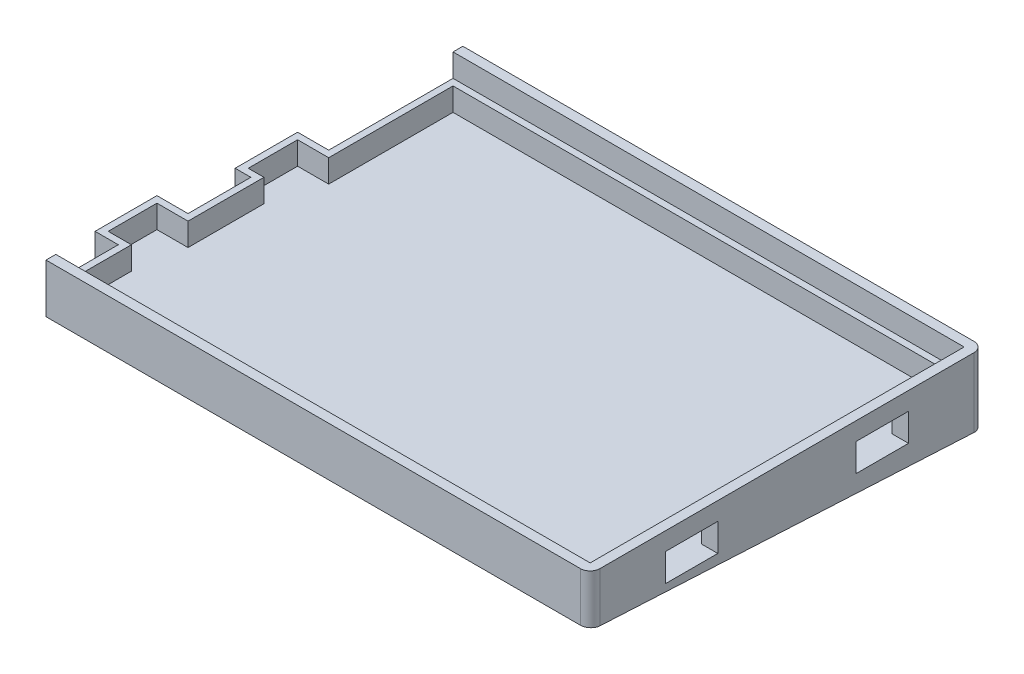
SolidWorks part; units mm, degrees
note: The reader was unsure of these and kept them because the rebuilt part matched: shared geometry of "Sketch3<3>", "Sketch5<4>", "Sketch5<6>".
ref_plane "Front Plane" through (0, 0, 0) normal (0, 0, 1) x (1, 0, 0)
ref_plane "Top Plane" through (0, 0, 0) normal (0, 1, 0) x (1, 0, 0)
ref_plane "Right Plane" through (0, 0, 0) normal (1, 0, 0) x (0, 0, -1)
sketch "Sketch3" plane through (0, 0, 0) normal (0, 1, 0) x (1, 0, 0)
  line L0 (0, 0) -> (0, 114.28)
  line L1 (0, 114.28) -> (-156.193, 114.28)
  line L2 (0, 0) -> (-163.3, 0)
  line L3 (-163.3, 0) -> (-163.3, 19.1)
  line L4 (-163.3, 19.1) -> (-170.4, 19.1)
  line L5 (-170.4, 19.1) -> (-170.4, 38)
  line L6 (-170.4, 38) -> (-160.9, 38)
  line L7 (-160.9, 38) -> (-160.9, 57.2)
  line L8 (-156.193, 114.28) -> (-156.193, 76.28)
  line L9 (-156.193, 76.28) -> (-165.693, 76.28)
  line L10 (-165.693, 76.28) -> (-165.693, 57.2)
  line L11 (-165.693, 57.2) -> (-160.9, 57.2)
  line L12 (3, -3) -> (-163.3, -3)
  line L13 (3, -3) -> (3, 117.28)
  line L14 (3, 117.28) -> (-156.193, 117.28)
  line L15 (-163.3, 0) -> (-163.3, -3)
  line L16 (-156.193, 117.28) -> (-156.193, 114.28)
  line L17 (0, 94.28) -> (3, 94.28)
  line L18 (0, 78.28) -> (3, 78.28)
  dimension "D1" = 114.28
  dimension "D2" = 156.193
  dimension "D3" = 163.3
  dimension "D4" = 19.1
  dimension "D5" = 18.9
  dimension "D6" = 7.1
  dimension "D7" = 9.5
  dimension "D8" = 19.2
  dimension "D9" = 38
  dimension "D10" = 9.5
  dimension "D11" = 3
  dimension "D12" = 16
  dimension "D13" = 20
extrude "Boss-Extrude2" add sketch "Sketch3" along normal blind 14 contours L14 L16 L1 L0 L2 L15 L12 L13 | L0 L17 L13 L14 L16 L1
extrude "Boss-Extrude3" add sketch "Sketch3<3>" against normal blind 1 contours L10 L11 L7 L6 L5 L4 L3 L2 L0 L1 L8 L9 | L14 L16 L1 L0 L2 L15 L12 L13
sketch "Sketch3<3>" plane through (0, 0, 0) normal (0, 1, 0) x (1, 0, 0) same geometry as "Sketch3"
sketch "Sketch4" plane through (3, 0, 0) normal (1, 0, 0) x (0, 0, -1)
  line L1 (117.28, -7.3036) -> (-3, -1)
  line L2 (-3, -1) -> (78.28, -1) construction
  line L5 (117.28, 14) -> (117.28, 0) construction
  line L6 (117.28, 0) -> (-3, 0)
  line L7 (-3, 14) -> (-3, -1) construction
  line L8 (-3, 0) -> (-3, -1)
  line L9 (117.28, 0) -> (117.28, -7.3036)
  dimension "D1" = 3
  dimension "D2" = 1
extrude "Boss-Extrude6" add sketch "Sketch4" against normal up to surface (159.193 mm away) up to face at (-156.193, -0.5, -95.28)
sketch "Sketch5" plane through (-156.193, 0, 0) normal (-1, 0, 0) x (0, 0, 1)
  line L0 (-76.28, 0) -> (3, 0)
  line L1 (0, 0) -> (3, 0) construction
  line L2 (3, 14) -> (3, -1) construction
  line L3 (3, 0) -> (3, -1)
  line L4 (3, -1) -> (-76.28, -5.1549)
  line L5 (-117.28, -7.3036) -> (3, -1) construction
  line L6 (-76.28, -5.1549) -> (-76.28, 0)
  line L7 (-19.1, 0) -> (-19.1, -2.1582)
  line L8 (-38, 0) -> (-38, -3.1487)
  line L9 (-57.2, 0) -> (-57.2, -4.1549)
  line M23 (3, -1) -> (-76.28, -1)
extrude "Boss-Extrude7" add sketch "Sketch5" along normal up to surface (4.707 mm away) contours L7 L4 M23
extrude "Boss-Extrude8" add sketch "Sketch5<4>" along normal up to surface (9.5 mm away) up to face at (-165.693, -0.5, -66.74)
sketch "Sketch5<4>" plane through (-156.193, 0, 0) normal (-1, 0, 0) x (0, 0, 1) same geometry as "Sketch5"
extrude "Boss-Extrude9" add sketch "Sketch5" along normal up to surface (7.107 mm away) contours L7 L4 M23 up to face at (-163.3, 4.3333, -5.3667)
extrude "Boss-Extrude10" add sketch "Sketch5<6>" along normal up to surface (14.207 mm away) up to face at (-170.4, -0.5, -28.55)
sketch "Sketch5<6>" plane through (-156.193, 0, 0) normal (-1, 0, 0) x (0, 0, 1) same geometry as "Sketch5"
sketch "Sketch7" plane through (0, 0, 0) normal (-1, 0, 0) x (0, 0, 1)
  line L0 (0, 0) -> (-20, 0)
  line L1 (3, 0) -> (-117.28, 0) construction
  line L2 (-20, 0) -> (-20, 14)
  line L3 (0, 14) -> (-78.28, 14) construction
  line L4 (-20, 14) -> (-36, 14)
  line L5 (-36, 14) -> (-36, 0)
  line L6 (-36, 0) -> (-20, 0)
  line L7 (-36, 8.5) -> (-20, 8.5)
  line M12 (-78.28, 0) -> (0, 0)
  dimension "D1" = 16
  dimension "D2" = 20
  dimension "D3" = 5.5
extrude "Cut-Extrude1" cut sketch "Sketch7" against normal blind 4 contours L7 L5 L2 M12
fillet "Fillet1" radius 3 1 edges at (3, 3.3482, -117.28)
fillet "Fillet2" radius 3 1 edges at (3, 6.5, 3)
sketch "Sketch8" plane through (0, 0, 0) normal (0, 1, 0) x (1, 0, 0)
  line L0 (-2, 112.28) -> (-154.193, 112.28)
  line L1 (-154.193, 112.28) -> (-154.193, 74.28)
  line L2 (-154.193, 74.28) -> (-163.693, 74.28)
  line L3 (-163.693, 74.28) -> (-163.693, 59.2)
  line L4 (-163.693, 59.2) -> (-158.9, 59.2)
  line L5 (-158.9, 59.2) -> (-158.9, 36)
  line L6 (-158.9, 36) -> (-168.4, 36)
  line L7 (-168.4, 36) -> (-168.4, 21.1)
  line L8 (-168.4, 21.1) -> (-161.3, 21.1)
  line L9 (-161.3, 21.1) -> (-161.3, 2)
  line L10 (-161.3, 2) -> (-2, 2)
  line L11 (-2, 2) -> (-2, 28)
  line L15 (-2, 28) -> (-2, 80.28)
  line L19 (-2, 92.28) -> (-2, 112.28)
  line L20 (3, 78.28) -> (3, 94.28)
  line L21 (3, 94.28) -> (0, 94.28)
  line L22 (0, 94.28) -> (0, 114.28)
  line L23 (0, 114.28) -> (-156.193, 114.28)
  line L24 (-156.193, 114.28) -> (-156.193, 76.28)
  line L25 (-156.193, 76.28) -> (-165.693, 76.28)
  line L26 (-165.693, 76.28) -> (-165.693, 57.2)
  line L27 (-165.693, 57.2) -> (-160.9, 57.2)
  line L28 (-160.9, 57.2) -> (-160.9, 38)
  line L29 (-160.9, 38) -> (-170.4, 38)
  line L30 (-170.4, 38) -> (-170.4, 19.1)
  line L31 (-170.4, 19.1) -> (-163.3, 19.1)
  line L32 (-163.3, 19.1) -> (-163.3, 0)
  line L33 (-163.3, 0) -> (0, 0)
  line L34 (0, 0) -> (0, 20)
  line L39 (0, 78.28) -> (3, 78.28)
  line L40 (3, 78.28) -> (3, 94.28)
  line L41 (3, 94.28) -> (0, 94.28)
  line L42 (0, 94.28) -> (0, 114.28)
  line L43 (0, 114.28) -> (-156.193, 114.28)
  line L44 (-156.193, 114.28) -> (-156.193, 76.28)
  line L45 (-156.193, 76.28) -> (-165.693, 76.28)
  line L46 (-165.693, 76.28) -> (-165.693, 57.2)
  line L47 (-165.693, 57.2) -> (-160.9, 57.2)
  line L48 (-160.9, 57.2) -> (-160.9, 38)
  line L49 (-160.9, 38) -> (-170.4, 38)
  line L50 (-170.4, 38) -> (-170.4, 19.1)
  line L51 (-170.4, 19.1) -> (-163.3, 19.1)
  line L52 (-163.3, 19.1) -> (-163.3, 0)
  line L53 (-163.3, 0) -> (0, 0)
  line L54 (0, 0) -> (0, 20)
  line L59 (0, 78.28) -> (3, 78.28)
  line L60 (1, 92.28) -> (-2, 92.28) construction
  line L61 (1, 80.28) -> (1, 92.28) construction
  line L62 (-2, 80.28) -> (1, 80.28) construction
  line L63 (-2, 28) -> (-2, 28) construction
  line L64 (-2, 28) -> (-2, 28) construction
  line L65 (-2, 28) -> (-2, 28) construction
  line L66 (0, 20) -> (-2, 20)
  line L67 (0, 36) -> (-2, 36)
  line L68 (-2, 36) -> (-2, 78.28)
  line L69 (-2, 78.28) -> (0, 78.28)
  line L70 (0, 94.28) -> (-2, 94.28)
  line L87 (0, 20) -> (0.0079, 19.846) construction
  line L88 (0.0079, 19.846) -> (0.0079, 36) construction
  line L89 (0.0079, 36) -> (0, 36) construction
  line L90 (0, 36) -> (0, 78.28) construction
  line L91 (0, 20) -> (3, 20)
  line L92 (0, 20) -> (3, 20)
  line L93 (3, 20) -> (3, 36)
  line L94 (3, 20) -> (3, 36)
  line L95 (3, 36) -> (0, 36)
  line L96 (3, 36) -> (0, 36)
  line L97 (0, 36) -> (0, 78.28)
  line L98 (0, 36) -> (0, 78.28)
  line M23 (0, 94.28) -> (0, 114.28)
  line M24 (0, 114.28) -> (-156.193, 114.28)
  line M25 (-156.193, 114.28) -> (-156.193, 76.28)
  line M26 (-156.193, 76.28) -> (-165.693, 76.28)
  line M27 (-165.693, 76.28) -> (-165.693, 57.2)
  line M28 (-165.693, 57.2) -> (-160.9, 57.2)
  line M29 (-160.9, 57.2) -> (-160.9, 38)
  line M30 (-160.9, 38) -> (-170.4, 38)
  line M31 (-170.4, 38) -> (-170.4, 19.1)
  line M32 (-170.4, 19.1) -> (-163.3, 19.1)
  line M33 (-163.3, 19.1) -> (-163.3, 0)
  line M34 (-163.3, 0) -> (0, 0)
  line M35 (0, 0) -> (0, 20)
  line M39 (0, 36) -> (0, 78.28)
  dimension "D1" = 0
  dimension "D2" = 2
extrude "Boss-Extrude11" add sketch "Sketch8" along normal blind 7 contours L70 L66 L11 L10 L9 L8 L7 L6 L5 L4 L3 L2 L1 L0 L19 M23 M24 M25 M26 M27 M28 M29 M30 M31 M32 M33 M34 M35 | L69 L15 L67 M39
sketch "Sketch9" plane through (0, 0, 0) normal (-1, 0, 0) x (0, 0, 1)
  line L0 (-78.28, 14) -> (-94.28, 14)
  line L1 (-94.28, 14) -> (-94.28, 8.5)
  line L2 (-94.28, 14) -> (-94.28, 7) construction
  line L3 (-94.28, 8.5) -> (-78.28, 8.5)
  line L4 (-78.28, 14) -> (-78.28, 7) construction
  line L5 (-78.28, 8.5) -> (-78.28, 14)
  dimension "D1" = 5.5
extrude "Boss-Extrude12" add sketch "Sketch9" against normal up to surface (3 mm away) up to face at (3, 5.962, -71.71)
